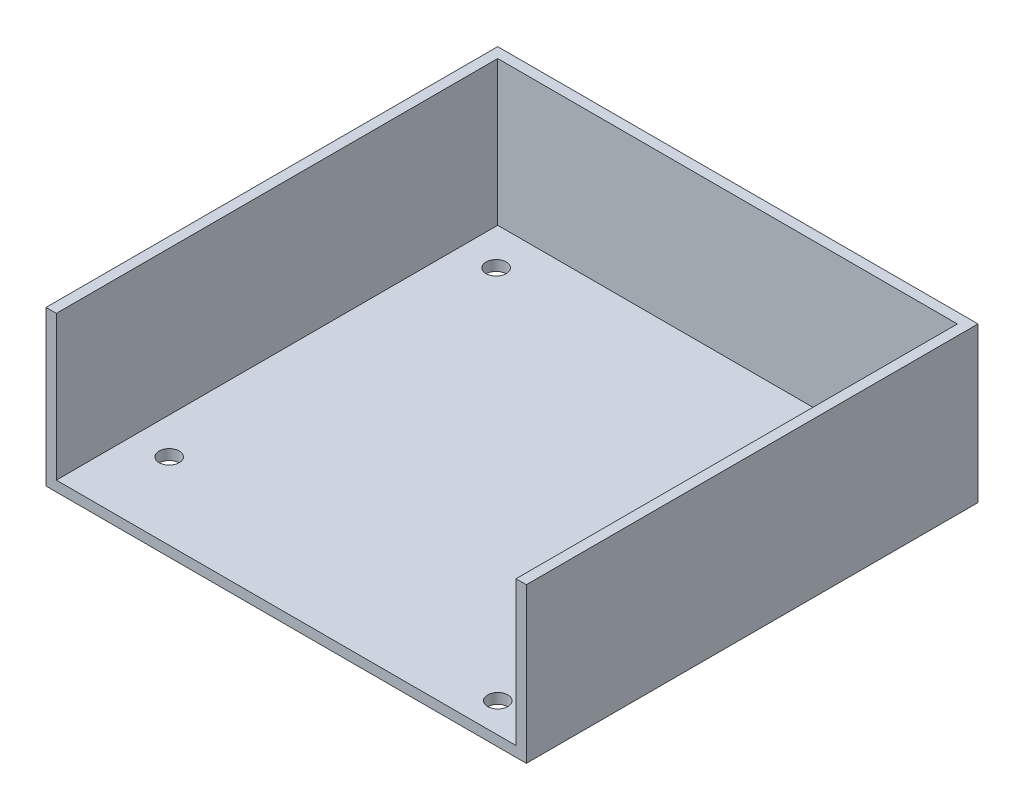
SolidWorks part; units mm, degrees
ref_plane "Front Plane" through (0, 0, 0) normal (0, 0, 1) x (1, 0, 0)
ref_plane "Top Plane" through (0, 0, 0) normal (0, 1, 0) x (1, 0, 0)
ref_plane "Right Plane" through (0, 0, 0) normal (1, 0, 0) x (0, 0, -1)
sketch "Sketch1" plane through (0, 0, 0) normal (0, 1, 0) x (1, 0, 0)
  line L1 (0, 0) -> (89.12, 0)
  line L2 (0, 0) -> (0, 85.57)
  line L3 (0, 85.57) -> (89.12, 85.57)
  line L4 (89.12, 0) -> (89.12, 85.57)
  dimension "D1" = 89.12
  dimension "D2" = 85.57
extrude "Boss-Extrude1" add sketch "Sketch1" along normal blind 2
sketch "Sketch3" plane through (0, 0, 0) normal (0, 0, 1) x (1, 0, 0)
  line L1 (0, 0) -> (-2, 0)
  line L2 (0, 0) -> (0, 30)
  line L3 (0, 30) -> (-2, 30)
  line L4 (-2, 0) -> (-2, 30)
  dimension "D1" = 2
  dimension "D2" = 30
extrude "Boss-Extrude2" add sketch "Sketch3" against normal blind 85.57
sketch "Sketch4" plane through (0, 0, 0) normal (0, 0, 1) x (1, 0, 0)
  line L1 (89.12, 0) -> (91.12, 0)
  line L2 (89.12, 0) -> (89.12, 30)
  line L3 (89.12, 30) -> (91.12, 30)
  line L4 (91.12, 0) -> (91.12, 30)
  dimension "D1" = 30
  dimension "D2" = 2
extrude "Boss-Extrude3" add sketch "Sketch4" against normal blind 85.57
sketch "Sketch5" plane through (0, 0, 0) normal (0, 1, 0) x (1, 0, 0)
  line L1 (-2, 85.57) -> (91.12, 85.57)
  line L2 (-2, 85.57) -> (-2, 87.57)
  line L3 (-2, 87.57) -> (91.12, 87.57)
  line L4 (91.12, 85.57) -> (91.12, 87.57)
  dimension "D1" = 2
extrude "Boss-Extrude4" add sketch "Sketch5" along normal blind 30
sketch "Sketch6" plane through (0, 0, 0) normal (0, 1, 0) x (1, 0, 0)
  line L0 (89.12, 0) -> (89.12, 5.755) construction
  line L1 (89.12, 0) -> (89.12, 85.57) construction
  line L2 (89.12, 5.755) -> (79.835, 5.755) construction
  line L3 (79.835, 5.755) -> (79.835, 0) construction
  line L4 (0, 0) -> (89.12, 0) construction
  circle A0 centre (79.835, 5.755) radius 1.96
  dimension "D3" = 3.92
extrude "Cut-Extrude2" cut sketch "Sketch6" along normal blind 30
sketch "Sketch7" plane through (0, 2, 0) normal (0, 1, 0) x (1, 0, 0)
  line L0 (89.12, 85.57) -> (82.285, 85.57) construction
  line L1 (0, 85.57) -> (89.12, 85.57) construction
  line L2 (82.285, 85.57) -> (82.285, 76.225) construction
  line L3 (82.285, 76.225) -> (89.12, 76.225) construction
  line L4 (89.12, 0) -> (89.12, 85.57) construction
  circle A0 centre (82.285, 76.225) radius 1.96
  dimension "D3" = 3.92
  dimension "D1" = 6.835
extrude "Cut-Extrude3" cut sketch "Sketch7" against normal blind 30
sketch "Sketch8" plane through (0, 0, 0) normal (0, 1, 0) x (1, 0, 0)
  line L0 (0, 85.57) -> (6.985, 85.57) construction
  line L1 (0, 85.57) -> (89.12, 85.57) construction
  line L2 (6.985, 85.57) -> (6.985, 78.28) construction
  line L3 (6.985, 78.28) -> (0, 78.28) construction
  line L4 (0, 85.57) -> (0, 0) construction
  circle A0 centre (6.985, 78.28) radius 1.96
  dimension "D3" = 3.92
  dimension "D1" = 7.29
extrude "Cut-Extrude4" cut sketch "Sketch8" along normal blind 30
sketch "Sketch9" plane through (0, 2, 0) normal (0, 1, 0) x (1, 0, 0)
  line L0 (0, 0) -> (0, 14.85) construction
  line L1 (0, 85.57) -> (0, 0) construction
  line L2 (0, 14.85) -> (7.035, 14.85) construction
  line L3 (7.035, 14.85) -> (7.035, 0) construction
  line L4 (0, 0) -> (89.12, 0) construction
  circle A0 centre (7.035, 14.85) radius 1.96
  dimension "D3" = 3.92
  dimension "D1" = 14.85
extrude "Cut-Extrude5" cut sketch "Sketch9" against normal blind 30
equation "\"tol1\"= 0.1cm"
equation "\"D1@Sketch1\"=8.812cm +\"tol1\""
equation "\"D2@Sketch1\"=8.457cm +\"tol1\""
equation "\"D1@Boss-Extrude2\"=8.457 +\"tol1\""
equation "\"D1@Boss-Extrude3\"=8.457 +\"tol1\""
equation "\"D1@Sketch6\"=0.5255 + \"tol2\""
equation "\"hole\"= 0.392cm"
equation "\"D3@Sketch6\"=\"hole\""
equation "\"tol2\"= \"tol1\" / 2"
equation "\"D2@Sketch6\"=0.8785 + \"tol2\""
equation "\"D2@Sketch9\"=0.6535 + \"tol2\""
equation "\"D3@Sketch9\"=\"hole\""
equation "\"D1@Sketch9\"=1.435 + \"tol2\""
equation "\"D2@Sketch8\"=0.6485 + \"tol2\""
equation "\"D1@Sketch8\"=0.679 + \"tol2\""
equation "\"D3@Sketch8\"=\"hole\""
equation "\"D3@Sketch7\"=\"hole\""
equation "\"D2@Sketch7\"=0.8845 + \"tol2\""
equation "\"D1@Sketch7\"=0.6335 + \"tol2\""
